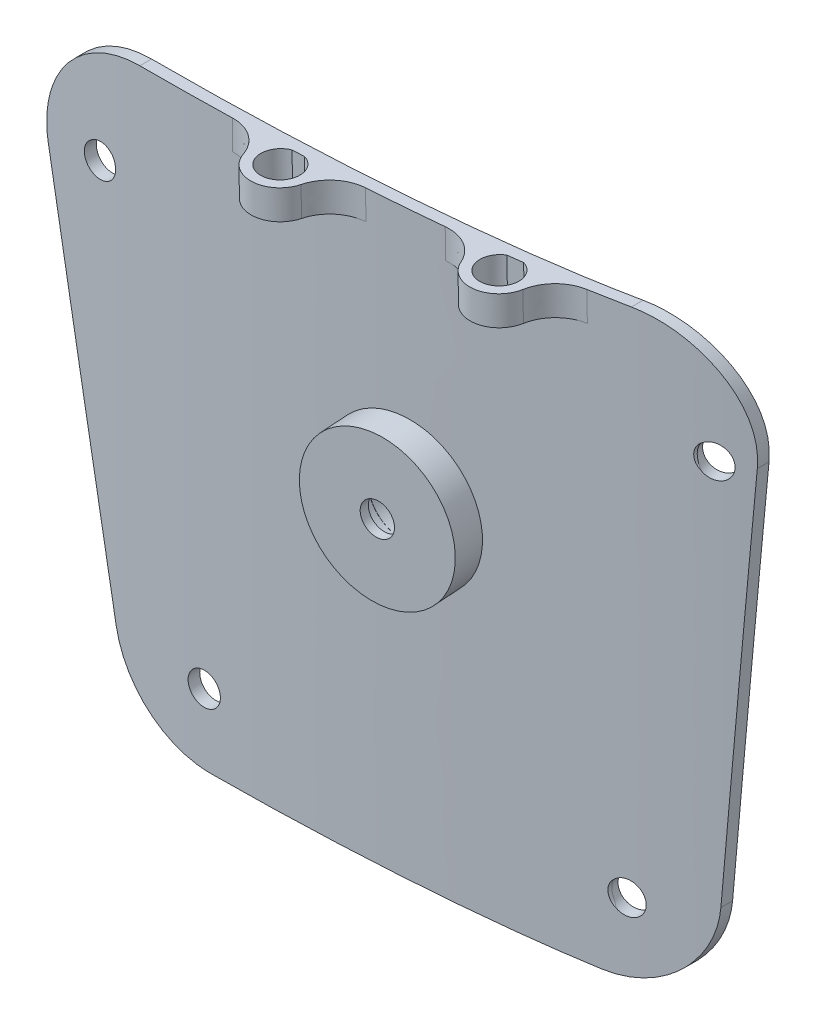
SolidWorks part; units mm, degrees
ref_plane "Front Plane" through (0, 0, 0) normal (0, 0, 1) x (1, 0, 0)
ref_plane "Top Plane" through (0, 0, 0) normal (0, 1, 0) x (1, 0, 0)
ref_plane "Right Plane" through (0, 0, 0) normal (1, 0, 0) x (0, 0, -1)
sketch "Sketch1" plane through (0, 0, 0) normal (0, 0, 1) x (1, 0, 0)
  line L0 (8.48, 36.3642) -> (19.3609, -22.641)
  line L1 (19.3609, -22.641) -> (74.3609, -22.641)
  line L2 (74.3609, -22.641) -> (78.473, 37.359)
  line L3 (78.473, 37.359) -> (8.48, 36.3642)
  dimension "D1" = 55
  dimension "D2" = 60
  dimension "D3" = 70
extrude "Boss-Extrude1" add sketch "Sketch1" along normal blind 20
sketch "Sketch2" plane through (0, 0, 0) normal (0, 1, 0) x (1, 0, 0)
  line L0 (-34.4394, -22.9262) -> (-34.4394, 11.6302)
  line L9 (-34.4394, 11.6302) -> (85.3158, 11.6302)
  line L13 (85.3158, 11.6302) -> (85.3158, -26.7671)
  line L14 (85.3158, -26.7671) -> (-34.4394, -22.9262)
  ellipse E0 centre (25.7637, -9.2394) end of major axis (-29.8558, -9.2394) minor radius 9.2394
  ellipse E1 centre (25.7637, -8.0394) end of major axis (-29.8558, -8.0394) minor radius 9.2394
  dimension "D1" = 1.2
fillet "Fillet1" radius 10 4 edges at (74.3609, -22.641, 10) (19.3609, -22.641, 10) (8.48, 36.3642, 10) (78.473, 37.359, 10)
extrude "Cut-Extrude1" cut sketch "Sketch2" against normal blind 100 and the other way blind 100 contours L14 L13 L9 L0 E1 E0 | E0 E1 | E0 E1 region at (-33.1818, 0, 5.648) region at (25.7637, 0, 8.6394) region at (25.7635, 0, -1.1167)
sketch "Sketch3" plane through (0, 0, 0) normal (0, 0, 1) x (1, 0, 0)
  circle A0 centre (16.2169, 26.1556) radius 1.55
  circle A1 centre (74.3863, 26.1556) radius 1.55
  circle A2 centre (46.8365, 10.8112) radius 1.55
  circle A3 centre (27.022, -15.3967) radius 1.55
  circle A4 centre (67.1179, -15.3967) radius 1.55
  circle A5 centre (67.1179, -15.3967) radius 19 construction
  circle A6 centre (74.3863, 26.1556) radius 19 construction
  circle A7 centre (46.8365, 10.8112) radius 19 construction
  circle A8 centre (16.2169, 26.1556) radius 19 construction
  circle A9 centre (27.022, -15.3967) radius 19 construction
  dimension "D1" = 3.1
  dimension "D2" = 38
extrude "Cut-Extrude4" cut sketch "Sketch3" against normal blind 10 and the other way blind 25
ref_plane "Plane1" through (1.5272, 0.6409, 18.5143) normal (0.0822, 0.0345, 0.996) x (0.9966, -0.0028, -0.0821)
sketch "Sketch4" plane through (1.5272, 0.6409, 18.5143) normal (0.0822, 0.0345, 0.996) x (0.9966, -0.0028, -0.0821)
  line L0 (64.7195, -8.486) -> (64.7195, -3.5422) construction
  line L1 (61.9695, -14.6348) -> (64.7195, -16.2225)
  line L2 (64.7195, -16.2225) -> (67.4695, -14.6348)
  line L3 (67.4695, -14.6348) -> (67.4695, -11.4594)
  line L4 (67.4695, -11.4594) -> (64.7195, -9.8717)
  line L5 (64.7195, -9.8717) -> (61.9695, -11.4594)
  line L6 (61.9695, -11.4594) -> (61.9695, -14.6348)
  line L7 (24.0299, -14.7724) -> (26.7799, -16.3601)
  line L8 (26.7799, -16.3601) -> (29.5299, -14.7724)
  line L9 (29.5299, -14.7724) -> (29.5299, -11.597)
  line L10 (29.5299, -11.597) -> (26.7799, -10.0093)
  line L11 (26.7799, -10.0093) -> (24.0299, -11.597)
  line L12 (24.0299, -11.597) -> (24.0299, -14.7724)
  line L13 (18.5904, 16.5438) -> (15.8404, 18.1316)
  line L14 (15.8404, 18.1316) -> (13.0904, 16.5438)
  line L15 (13.0904, 16.5438) -> (13.0904, 13.3684)
  line L16 (13.0904, 13.3684) -> (15.8404, 11.7807)
  line L17 (15.8404, 11.7807) -> (18.5904, 13.3684)
  line L18 (18.5904, 13.3684) -> (18.5904, 16.5438)
  line L19 (40.4486, 29.0762) -> (43.1986, 27.4885)
  line L20 (43.1986, 27.4885) -> (45.9486, 29.0762)
  line L21 (45.9486, 29.0762) -> (45.9486, 32.2516)
  line L22 (45.9486, 32.2516) -> (43.1986, 33.8393)
  line L23 (43.1986, 33.8393) -> (40.4486, 32.2516)
  line L24 (40.4486, 32.2516) -> (40.4486, 29.0762)
  line L25 (67.8225, 15.8227) -> (70.5725, 14.235)
  line L26 (70.5725, 14.235) -> (73.3225, 15.8227)
  line L27 (73.3225, 15.8227) -> (73.3225, 18.9981)
  line L28 (73.3225, 18.9981) -> (70.5725, 20.5859)
  line L29 (70.5725, 20.5859) -> (67.8225, 18.9981)
  line L30 (67.8225, 18.9981) -> (67.8225, 15.8227)
  line L31 (19.7904, 17.2367) -> (15.8404, 19.5172)
  line L32 (15.8404, 19.5172) -> (11.8904, 17.2367)
  line L33 (11.8904, 17.2367) -> (11.8904, 12.6756)
  line L34 (11.8904, 12.6756) -> (15.8404, 10.3951)
  line L35 (15.8404, 10.3951) -> (19.7904, 12.6756)
  line L36 (19.7904, 12.6756) -> (19.7904, 17.2367)
  line L37 (43.1986, 26.1029) -> (47.1486, 28.3834)
  line L38 (47.1486, 28.3834) -> (47.1486, 32.9445)
  line L39 (47.1486, 32.9445) -> (43.1986, 35.225)
  line L40 (43.1986, 35.225) -> (39.2486, 32.9445)
  line L41 (39.2486, 32.9445) -> (39.2486, 28.3834)
  line L42 (39.2486, 28.3834) -> (43.1986, 26.1029)
  line L43 (70.5725, 21.9715) -> (66.6225, 19.691)
  line L44 (66.6225, 19.691) -> (66.6225, 15.1299)
  line L45 (66.6225, 15.1299) -> (70.5725, 12.8494)
  line L46 (70.5725, 12.8494) -> (74.5225, 15.1299)
  line L47 (74.5225, 15.1299) -> (74.5225, 19.691)
  line L48 (74.5225, 19.691) -> (70.5725, 21.9715)
  line L49 (64.7195, -8.486) -> (60.7695, -10.7665)
  line L50 (60.7695, -10.7665) -> (60.7695, -15.3276)
  line L51 (60.7695, -15.3276) -> (64.7195, -17.6081)
  line L52 (64.7195, -17.6081) -> (68.6695, -15.3276)
  line L53 (68.6695, -15.3276) -> (68.6695, -10.7665)
  line L54 (68.6695, -10.7665) -> (64.7195, -8.486)
  line L55 (70.5725, 21.9715) -> (70.5725, 20.5859) construction
  line L56 (26.7799, -8.6236) -> (22.8299, -10.9042)
  line L57 (22.8299, -10.9042) -> (22.8299, -15.4652)
  line L58 (22.8299, -15.4652) -> (26.7799, -17.7458)
  line L59 (26.7799, -17.7458) -> (30.7299, -15.4652)
  line L60 (30.7299, -15.4652) -> (30.7299, -10.9042)
  line L61 (30.7299, -10.9042) -> (26.7799, -8.6236)
  line L62 (64.7195, -9.8717) -> (64.7195, -8.486) construction
  circle A0 centre (64.7195, -13.0471) radius 2.75 construction
  circle A1 centre (26.7799, -13.1847) radius 2.75 construction
  circle A2 centre (15.8404, 14.9561) radius 2.75 construction
  circle A3 centre (43.1986, 30.6639) radius 2.75 construction
  circle A4 centre (70.5725, 17.4104) radius 2.75 construction
  circle A6 centre (43.1986, 30.6639) radius 1.6732
  circle A7 centre (70.5725, 17.4104) radius 1.7162
  circle A8 centre (64.7195, -13.0471) radius 1.4882
  circle A9 centre (26.7799, -13.1847) radius 1.6102
  circle A10 centre (15.8404, 14.9561) radius 1.6379
  circle A11 centre (15.8404, 14.9561) radius 3.95 construction
  circle A12 centre (43.1986, 30.6639) radius 3.95 construction
  circle A13 centre (70.5725, 17.4104) radius 3.95 construction
  circle A14 centre (64.7195, -13.0471) radius 3.95 construction
  circle A15 centre (26.7799, -13.1847) radius 3.95 construction
  dimension "D1" = 5.5
  dimension "D2" = 5.5
  dimension "D3" = 5.5
  dimension "D4" = 5.5
  dimension "D5" = 5.5
  dimension "D6" = 1.2
  dimension "D7" = 1.2
  dimension "D8" = 1.2
  dimension "D9" = 1.2
  dimension "D10" = 1.2
extrude "Boss-Extrude4" [suppressed] add sketch "Sketch4" along normal up to surface and the other way blind 1 contours L60 L61 L56 L57 L58 L59 L12 L11 L10 L9 L8 L7 | L35 L36 L31 L32 L33 L34 L18 L17 L16 L15 L14 L13 | L41 L42 L37 L38 L39 L40 L24 L23 L22 L21 L20 L19 | L47 L48 L43 L44 L45 L46 L30 L29 L28 L27 L26 L25 | L53 L54 L49 L50 L51 L52 L6 L5 L4 L3 L2 L1 up to face at (42.9959, 5.2796, 16.4437)
sketch "Sketch5" [suppressed] plane through (1.445, 0.6064, 17.5183) normal (-0.0822, -0.0345, -0.996) x (-0.9966, 0.0028, 0.0821)
  circle A0 centre (-43.0742, 30.662) radius 6.5878
extrude "Cut-Extrude5" [suppressed] cut sketch "Sketch5" against normal blind 2
fillet "Fillet2" [suppressed] radius 1.5
fillet "Fillet3" [suppressed] radius 1.5
fillet "Fillet4" [suppressed] radius 1
sketch3d "3DSketch4"
  point P0 (15.2875, 24.9153, 17.1134)
  point P1 (16.0993, 26.3266, 17.1383)
  point P2 (14.6669, 26.1556, 17.0931)
  point P3 (17.3452, 27.2184, 17.1724)
  point P4 (14.6669, 26.1556, 17.0931)
  point P5 (17.6333, 25.5261, 17.1796)
  point P6 (14.6669, 26.1556, 17.0931)
ref_plane "Plane3" through (-0.4619, -0.0269, 16.6357) normal (-0.0278, -0.0016, 0.9996) x (0.9996, 0, 0.0278)
ref_plane "Plane4" through (-0.4342, -0.0253, 15.6361) normal (-0.0278, -0.0016, 0.9996) x (0.9996, 0, 0.0278)
sketch3d "3DSketch5"
  point P2 (45.4626, 11.5287, 16.6799)
  point P3 (45.3003, 10.209, 16.6901)
  point P4 (45.2865, 10.8112, 16.691)
  point P5 (45.5319, 9.9742, 16.6756)
  point P6 (45.2865, 10.8112, 16.691)
  point P7 (46.3238, 9.3485, 16.6244)
  point P8 (45.2865, 10.8112, 16.691)
  point P9 (47.4812, 9.4017, 16.5454)
  point P10 (45.2865, 10.8112, 16.691)
  point P11 (48.369, 10.5795, 16.4813)
  point P12 (45.2865, 10.8112, 16.691)
  point P13 (48.0297, 11.8005, 16.5006)
  point P14 (47.1368, 12.3319, 16.5694)
  point P15 (45.2865, 10.8112, 16.691)
ref_plane "Plane5" through (1.3602, 0.0344, 19.739) normal (-0.0687, -0.0017, -0.9976) x (-0.9976, 0.0001, 0.0687)
ref_plane "Plane6" through (1.4427, 0.0365, 20.9362) normal (-0.0687, -0.0017, -0.9976) x (-0.9976, 0.0001, 0.0687)
sketch "Sketch6" plane through (-0.4342, -0.0253, 15.6361) normal (-0.0278, -0.0016, 0.9996) x (0.9996, 0, 0.0278)
  circle A0 centre (16.6314, 25.9967) radius 1.65
  dimension "D1" = 3.3
extrude "Cut-Extrude6" cut sketch "Sketch6" against normal blind 10 and the other way blind 10
sketch "Sketch7" plane through (1.4427, 0.0365, 20.9362) normal (-0.0687, -0.0017, -0.9976) x (-0.9976, 0.0001, 0.0687)
  circle A0 centre (-45.496, 10.7782) radius 1.65
  dimension "D1" = 3.3
extrude "Cut-Extrude7" cut sketch "Sketch7" against normal blind 10 and the other way blind 10
sketch3d "3DSketch6"
  spline S6 degree 2 poles (27.0581, -16.9463, 18.4763) (29.9634, -15.9935, 18.4591) (27.0582, -13.8471, 18.4763) knots 0 0 0 1 1 1
  spline S7 degree 3 poles (25.472, -15.1919, 18.4787) (25.472, -15.4991, 18.4787) (25.4821, -15.5998, 18.4787) (25.5215, -15.7979, 18.4787) (25.5513, -15.8963, 18.4788) (25.6291, -16.084, 18.4788) (25.6767, -16.1731, 18.4788) (25.7892, -16.3415, 18.4788) (25.8546, -16.4213, 18.4788) (26.0691, -16.6358, 18.4787) (26.2421, -16.7513, 18.4785) (26.6151, -16.9059, 18.4778) (26.8191, -16.9466, 18.4772) (27.1223, -16.9468, 18.4761) (27.225, -16.9367, 18.4757) (27.4238, -16.8972, 18.4747) (27.5204, -16.8679, 18.4742) (27.7081, -16.7903, 18.4732) (27.7988, -16.7418, 18.4726) (27.9668, -16.6296, 18.4716) (28.0451, -16.5656, 18.4711) (28.2622, -16.3487, 18.4695) (28.376, -16.1781, 18.4686) (28.4928, -15.8963, 18.4677) (28.5222, -15.7997, 18.4675) (28.5618, -15.6011, 18.4671) (28.572, -15.4984, 18.467) (28.5721, -15.1949, 18.467) (28.5316, -14.9911, 18.4674) (28.3773, -14.6179, 18.4686) (28.2619, -14.4448, 18.4695) (28.0477, -14.2302, 18.471) (27.9681, -14.1647, 18.4716) (27.7995, -14.052, 18.4726) (27.7106, -14.0043, 18.4732) (27.5232, -13.9264, 18.4742) (27.4246, -13.8965, 18.4747) (27.2264, -13.8569, 18.4756) (27.1258, -13.8468, 18.4761) (26.8192, -13.8465, 18.4772) (26.618, -13.8865, 18.4778) (26.3359, -14.0031, 18.4784) (26.2468, -14.0507, 18.4785) (26.0784, -14.1629, 18.4787) (25.9985, -14.2283, 18.4788) (25.7837, -14.4428, 18.4789) (25.6681, -14.6155, 18.4788) (25.5132, -14.9885, 18.4787) (25.472, -15.1919, 18.4787) (25.472, -15.4991, 18.4787) (25.4821, -15.5998, 18.4787) knots -0.0625 -0.0625 0 0 0.03125 0.03125 0.0625 0.0625 0.09375 0.09375 0.125 0.125 0.1875 0.1875 0.25 0.25 0.28125 0.28125 0.3125 0.3125 0.34375 0.34375 0.375 0.375 0.4375 0.4375 0.46875 0.46875 0.5 0.5 0.5625 0.5625 0.625 0.625 0.65625 0.65625 0.6875 0.6875 0.71875 0.71875 0.75 0.75 0.8125 0.8125 0.84375 0.84375 0.875 0.875 0.9375 0.9375 1 1 1.03125 1.03125 1.0625 only from (25.472, -15.3967, 18.4787) to (25.472, -15.3967, 18.4787) construction
ref_plane "Plane7" through (0.1108, 0, 18.6365) normal (0.0059, 0, 1) x (1, 0, -0.0059)
ref_plane "Plane8" through (0.1179, 0, 19.8365) normal (0.0059, 0, 1) x (1, 0, -0.0059)
sketch "Sketch8" plane through (0.1179, 0, 19.8365) normal (0.0059, 0, 1) x (1, 0, -0.0059)
  circle A0 centre (26.8542, -15.4402) radius 1.65
  dimension "D1" = 3.3
extrude "Cut-Extrude8" cut sketch "Sketch8" against normal blind 10 and the other way blind 10
sketch3d "3DSketch7"
  point P3 (67.6075, -13.926, 14.1263)
  point P4 (67.789, -13.9995, 14.0917)
  point P5 (65.5679, -15.3967, 14.4927)
  point P6 (65.5679, -15.3967, 14.4927)
  point P7 (67.9095, -14.0641, 14.0685)
  point P8 (65.5679, -15.3967, 14.4927)
  point P9 (66.3505, -16.7433, 14.3568)
  point P10 (65.5679, -15.3967, 14.4927)
  point P11 (67.1997, -16.9445, 14.2028)
  point P12 (65.5679, -15.3967, 14.4927)
  point P13 (67.9774, -16.6866, 14.0554)
  point P14 (65.5679, -15.3967, 14.4927)
  point P15 (66.2819, -14.0915, 14.3689)
  point P16 (65.5679, -15.3967, 14.4927)
  point P17 (66.4764, -13.9857, 14.3344)
  point P18 (65.5679, -15.3967, 14.4927)
  point P19 (66.7337, -13.8951, 14.4068)
  point P20 (66.9779, -13.853, 14.2437)
  point P21 (65.5679, -15.3967, 14.4927)
ref_plane "Plane9" through (4.7257, 0.0126, 25.6877) normal (-0.1809, -0.0005, -0.9835) x (-0.9835, 0.0007, 0.1809)
ref_plane "Plane10" through (4.9428, 0.0132, 26.8679) normal (-0.1809, -0.0005, -0.9835) x (-0.9835, 0.0007, 0.1809)
sketch "Sketch9" plane through (4.9428, 0.0132, 26.8679) normal (-0.1809, -0.0005, -0.9835) x (-0.9835, 0.0007, 0.1809)
  circle A0 centre (-63.3807, -15.3525) radius 1.65
  dimension "D1" = 3.3
extrude "Cut-Extrude9" cut sketch "Sketch9" against normal blind 10 and the other way blind 10
sketch3d "3DSketch8"
  point P1 (73.7438, 24.7451, 12.7127)
  point P2 (75.3196, 24.918, 12.2345)
  point P3 (72.8363, 26.1556, 12.9608)
  point P4 (72.8363, 26.1556, 12.9608)
  point P6 (73.3932, 27.3456, 12.8107)
  point P7 (72.8459, 26.328, 12.9583)
  point P8 (72.8363, 26.1556, 12.9608)
  point P9 (73.0651, 25.3451, 12.8999)
  point P10 (72.8363, 26.1556, 12.9608)
ref_plane "Plane11" through (9.7771, 0.5194, 32.4024) normal (-0.2888, -0.0153, -0.9573) x (-0.9574, 0.0046, 0.2888)
ref_plane "Plane12" through (10.1237, 0.5378, 33.5511) normal (-0.2888, -0.0153, -0.9573) x (-0.9574, 0.0046, 0.2888)
sketch "Sketch10" plane through (10.1237, 0.5378, 33.5511) normal (-0.2888, -0.0153, -0.9573) x (-0.9574, 0.0046, 0.2888)
  circle A0 centre (-67.2759, 25.9055) radius 1.65
  dimension "D1" = 3.3
extrude "Cut-Extrude10" cut sketch "Sketch10" against normal blind 10 and the other way blind 10
sketch "Sketch11" plane through (1.4427, 0.0365, 20.9362) normal (-0.0687, -0.0017, -0.9976) x (-0.9976, 0.0001, 0.0687)
  circle A0 centre (-45.4795, 10.7691) radius 1.65
  circle A1 centre (-45.4795, 10.7691) radius 7.5
  dimension "D1" = 15
  dimension "D2" = 3.3
extrude "Boss-Extrude5" add sketch "Sketch11" against normal blind 3
ref_plane "Plane13" through (1.3464, 0.0341, 19.5395) normal (0.0687, 0.0017, 0.9976) x (0.9976, -0.0001, -0.0687)
sketch "Sketch12" plane through (1.3464, 0.0341, 19.5395) normal (0.0687, 0.0017, 0.9976) x (0.9976, -0.0001, -0.0687)
  circle A0 centre (45.4796, 10.7687) radius 3.5023
  dimension "D1" = 7.0046
extrude "Cut-Extrude11" cut sketch "Sketch12" along normal blind 3.5 contours A0 | A0 | A0 region at (46.7184, 10.7973, 16.3942)
sketch "Sketch16" plane through (-0.5151, 36.2363, 0) normal (-0.0142, 0.9999, 0) x (0.9999, 0.0142, 0)
  line L0 (47.3714, -17.789) -> (48.0189, -26.7049) construction
  circle A0 centre (57.9629, -18.6858) radius 3
  circle A1 centre (57.9629, -18.6858) radius 2
  circle A2 centre (37.0206, -20.2066) radius 2
  circle A3 centre (37.0206, -20.2066) radius 3
  ellipse E0 centre (26.2814, -9.2394) end of major axis (-29.3437, -9.2394) minor radius 9.2394 (20.8365, -18.4345) -> (68.1335, -15.3255) ccw construction
  dimension "D1" = 4
  dimension "D2" = 6
extrude "Boss-Extrude6" add sketch "Sketch16" against normal blind 3
fillet "Fillet5" radius 4 4 edges
mirror "Mirror2" [suppressed] about plane through (0, 0, 0) normal (1, 0, 0) of bodies 114
sketch "Sketch14" plane through (0, 0, 0) normal (1, 0, 0) x (0, 0, -1)
  circle A0 centre (-13.6451, 8.6501) radius 65.5667
extrude "Cut-Extrude12" [suppressed] cut sketch "Sketch14" along normal blind 93
